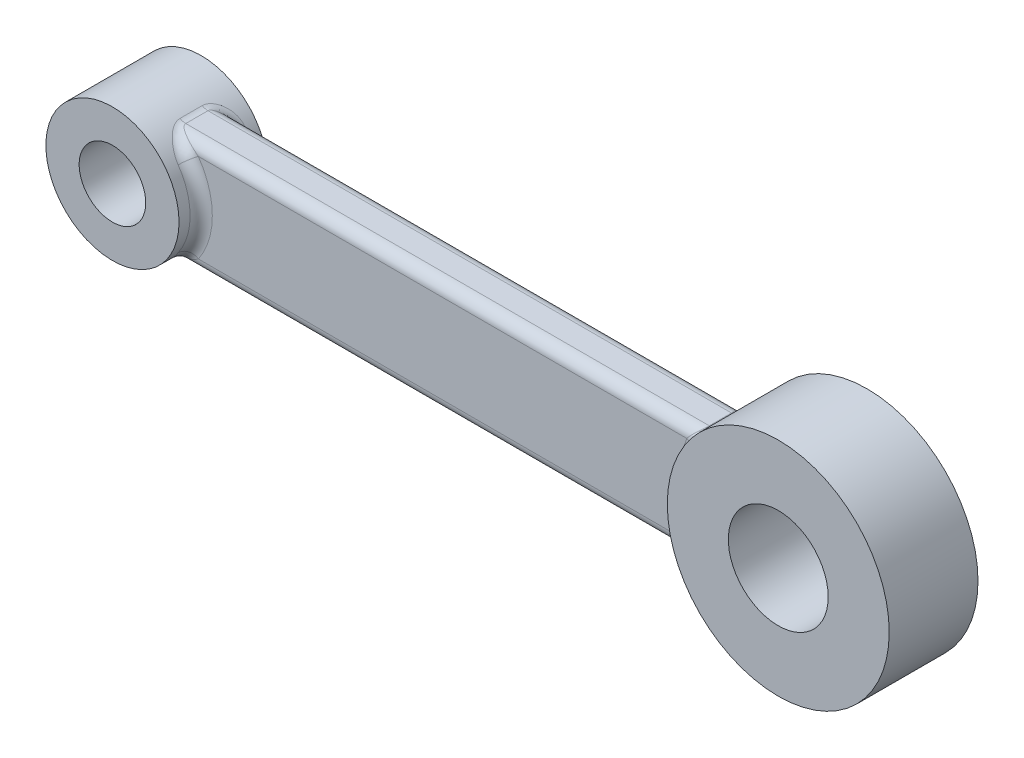
SolidWorks part; units mm, degrees
ref_plane "Front Plane" through (0, 0, 0) normal (0, 0, 1) x (1, 0, 0)
ref_plane "Top Plane" through (0, 0, 0) normal (0, 1, 0) x (1, 0, 0)
ref_plane "Right Plane" through (0, 0, 0) normal (1, 0, 0) x (0, 0, -1)
sketch "Sketch1" plane through (0, 0, 0) normal (0, 0, 1) x (1, 0, 0)
  line L1 (-15, -2.5) -> (15, -2.5)
  line L2 (-15, -2.5) -> (-15, 2.5)
  line L3 (-15, 2.5) -> (15, 2.5)
  line L4 (15, -2.5) -> (15, 2.5)
  line L5 (-15, -2.5) -> (15, 2.5) construction
  line L6 (-15, 2.5) -> (15, -2.5) construction
  point P0 (0, 0)
  dimension "D1" = 5
  dimension "D2" = 30
extrude "Boss-Extrude1" add sketch "Sketch1" along normal mid plane 2
sketch "Sketch2" plane through (0, 0, 0) normal (0, 0, 1) x (1, 0, 0)
  line L0 (-15, 2.5) -> (-15, -2.5) construction
  line L1 (15, -2.5) -> (15, 2.5) construction
  circle A0 centre (-15, 0) radius 3
  circle A1 centre (15, 0) radius 5
  dimension "D1" = 6
  dimension "D2" = 10
extrude "Boss-Extrude2" add sketch "Sketch2" along normal mid plane 4
sketch "Sketch3" plane through (0, 0, 2) normal (0, 0, 1) x (1, 0, 0)
  circle A0 centre (-15, 0) radius 1.5
  circle A1 centre (15, 0) radius 2.25
  dimension "D1" = 3
  dimension "D2" = 4.5
extrude "Cut-Extrude1" cut sketch "Sketch3" against normal through all
fillet "Fillet1" radius 0.5 4 edges at (-1.3359, -2.5, 1) (-1.3359, 2.5, -1) (-1.3359, 2.5, 1) (-1.3359, -2.5, -1)
fillet "Fillet2" radius 0.5 16 edges at (10.6204, 2.4123, 0.7829) (10.6699, 2.5, 0) (10.5801, 2.3376, -0.8688) (10, 0, -1) (10.6204, -2.4123, -0.7829) (10.6699, -2.5, 0) (10.5801, -2.3376, 0.8688) (-13.2762, -2.4553, 0.7066) (-13.3417, -2.5, 0) (-13.1981, -2.3986, -0.8019) (-12, 0, -1) (-13.2762, 2.4553, -0.7066) (-13.3417, 2.5, 0) (10, 0, 1) (-13.1981, 2.3986, 0.8019) (-12, 0, 1)
